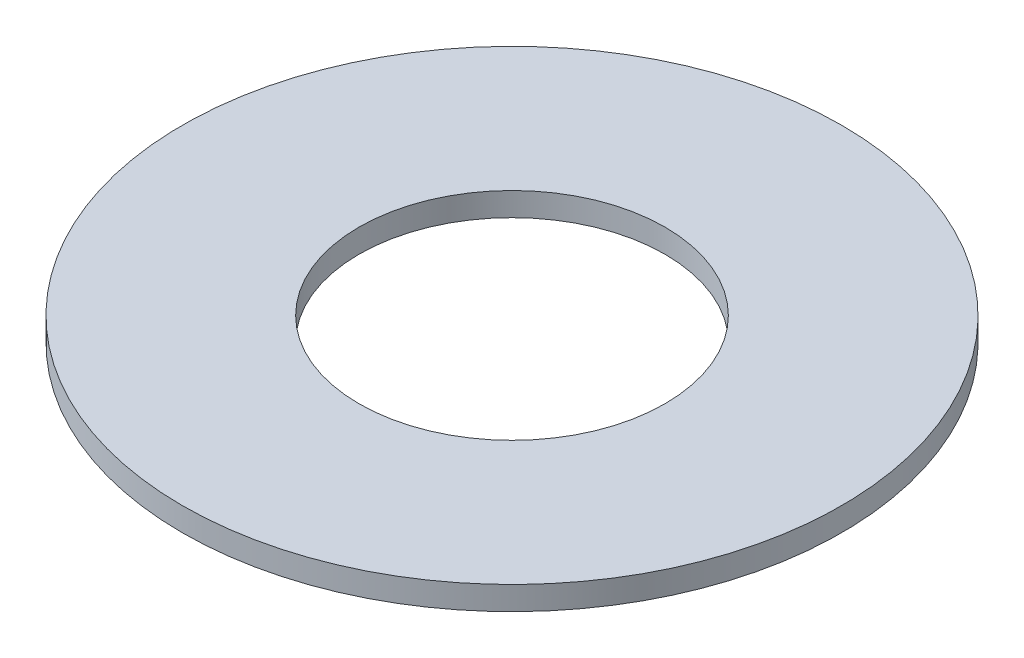
SolidWorks part; units mm, degrees
ref_plane "Front Plane" through (0, 0, 0) normal (0, 0, 1) x (1, 0, 0)
ref_plane "Top Plane" through (0, 0, 0) normal (0, 1, 0) x (1, 0, 0)
ref_plane "Right Plane" through (0, 0, 0) normal (1, 0, 0) x (0, 0, -1)
sketch "Sketch1" plane through (0, 0, 0) normal (0, 1, 0) x (1, 0, 0)
  circle A0 centre (0, 0) radius 70
  dimension "FLANGE_OD" = 140
extrude "Boss-Extrude1" add sketch "Sketch1" along normal blind 5
sketch "Sketch2" plane through (0, 0, 0) normal (0, 1, 0) x (1, 0, 0)
  circle A0 centre (0, 0) radius 32.5
  dimension "BORE_D" = 65
extrude "Cut-Extrude1" cut sketch "Sketch2" along normal through all
sketch "Sketch3" plane through (0, 5, 0) normal (0, 1, 0) x (1, 0, 0)
  circle A0 centre (0, 0) radius 19.6719 construction
  circle A1 centre (-19.6719, 0) radius 4.1481
  dimension "BOLT_D" = 8.2962
  dimension "BOLT_PCD" = 39.3437
extrude "Cut-Extrude2" cut sketch "Sketch3" against normal blind 4.0422 rebuild error yes
pattern_circular "CirPattern1" count 4 over 360 rebuild error yes
